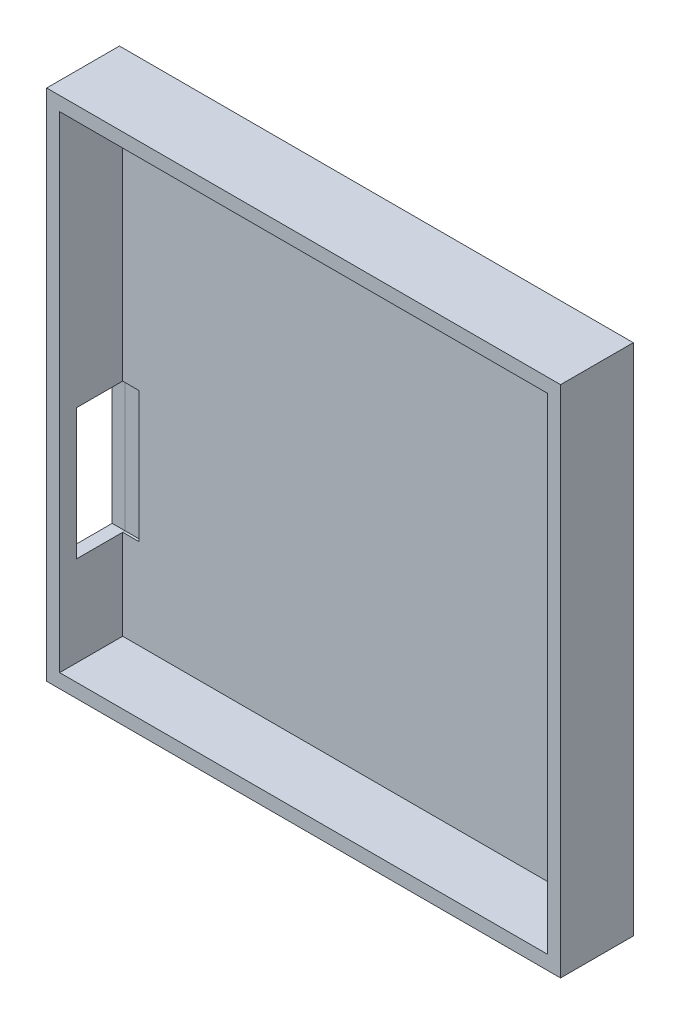
SolidWorks part; units mm, degrees
note: The reader was unsure of these and kept them because the rebuilt part matched: shared geometry of "Sketch2<5>".
ref_plane "Front Plane" through (0, 0, 0) normal (0, 0, 1) x (1, 0, 0)
ref_plane "Top Plane" through (0, 0, 0) normal (0, 1, 0) x (1, 0, 0)
ref_plane "Right Plane" through (0, 0, 0) normal (1, 0, 0) x (0, 0, -1)
sketch "Model"
sketch "Sketch2" plane through (0, 0, 0) normal (0, 0, 1) x (1, 0, 0)
  line L5 (98.0037, -146.75) -> (204.0037, -146.75)
  line L6 (98.0037, -146.75) -> (98.0037, -40.75)
  line L7 (98.0037, -40.75) -> (204.0037, -40.75)
  line L8 (204.0037, -146.75) -> (204.0037, -40.75)
  line L13 (201.3332, -143.8601) -> (100.6742, -43.6399) construction
  line L14 (201.3332, -43.6399) -> (100.6742, -143.8601) construction
  line L15 (100.6742, -143.8601) -> (201.3332, -143.8601)
  line L16 (100.6742, -143.8601) -> (100.6742, -43.6399)
  line L17 (100.6742, -43.6399) -> (201.3332, -43.6399)
  line L18 (201.3332, -143.8601) -> (201.3332, -43.6399)
  line L19 (100.6742, -143.8601) -> (201.3332, -43.6399) construction
  line L20 (100.6742, -43.6399) -> (201.3332, -143.8601) construction
  point P5 (151.0037, -93.75)
  point P7 (151.0037, -93.75)
  dimension "D1" = 106
  dimension "D2" = 106
extrude "Boss-Extrude2" add sketch "Sketch2" along normal blind 15
extrude "Boss-Extrude5" add sketch "Sketch2<5>" along normal blind 2 separate body
sketch "Sketch2<5>" plane through (0, 0, 0) normal (0, 0, 1) x (1, 0, 0) same geometry as "Sketch2"
sketch "Sketch6" plane through (98.0037, 0, 0) normal (-1, 0, 0) x (0, 0, 1)
  line L0 (0, -84.6) -> (0, -114.9) construction
  line L1 (1.5, -98.2791) -> (11.5, -98.2791)
  line L2 (1.5, -98.2791) -> (1.5, -125.2791)
  line L3 (1.5, -125.2791) -> (11.5, -125.2791)
  line L4 (11.5, -98.2791) -> (11.5, -125.2791)
  dimension "D1" = 27
  dimension "D2" = 10
  dimension "D3" = 1.5
extrude "Cut-Extrude1" cut sketch "Sketch6" against normal blind 6
